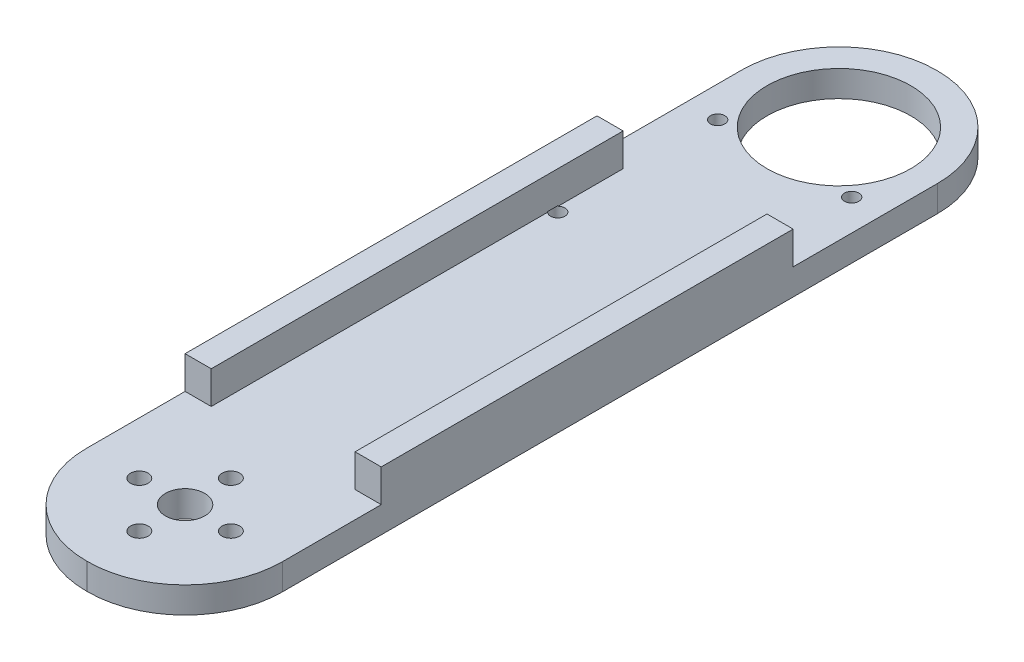
SolidWorks part; units mm, degrees
ref_plane "Front Plane" through (0, 0, 0) normal (0, 0, 1) x (1, 0, 0)
ref_plane "Top Plane" through (0, 0, 0) normal (0, 1, 0) x (1, 0, 0)
ref_plane "Right Plane" through (0, 0, 0) normal (1, 0, 0) x (0, 0, -1)
ref_plane "PY_p16_000" through (0, 16, 0) normal (0, 1, 0) x (1, 0, 0)
sketch "S_prism1" plane through (0, 16, 0) normal (0, 1, 0) x (1, 0, 0)
  line L0 (-0.1, -15) -> (0.1, -15)
  line L1 (15, -0.1) -> (15, 100.1)
  line L2 (0.1, 115) -> (-0.1, 115)
  line L3 (-15, 100.1) -> (-15, -0.1)
  arc A0 (-15, -0.1) -> (-0.1, -15) centre (-0.1, -0.1) ccw
  arc A1 (0.1, -15) -> (15, -0.1) centre (0.1, -0.1) ccw
  arc A2 (15, 100.1) -> (0.1, 115) centre (0.1, 100.1) ccw
  arc A3 (-0.1, 115) -> (-15, 100.1) centre (-0.1, 100.1) ccw
extrude "Boss_1" add sketch "S_prism1" along normal blind 4
ref_plane "PZ_m78_000" through (0, 0, -78) normal (0, 0, 1) x (1, 0, 0)
sketch "S_box2" plane through (0, 0, -78) normal (0, 0, 1) x (1, 0, 0)
  line L0 (-15, 19.5) -> (-11, 19.5)
  line L1 (-11, 19.5) -> (-11, 25)
  line L2 (-11, 25) -> (-15, 25)
  line L3 (-15, 25) -> (-15, 19.5)
  dimension "P1" = 15
  dimension "P2" = 19.5
  dimension "P3" = 11
  dimension "P4" = 19.5
  dimension "P5" = 11
  dimension "P6" = 25
  dimension "P7" = 15
  dimension "P8" = 25
extrude "Boss_2" add sketch "S_box2" along normal blind 63
sketch "S_box3" plane through (0, 0, -78) normal (0, 0, 1) x (1, 0, 0)
  line L0 (11, 19.5) -> (15, 19.5)
  line L1 (15, 19.5) -> (15, 25)
  line L2 (15, 25) -> (11, 25)
  line L3 (11, 25) -> (11, 19.5)
  dimension "P1" = 11
  dimension "P2" = 19.5
  dimension "P3" = 15
  dimension "P4" = 19.5
  dimension "P5" = 15
  dimension "P6" = 25
  dimension "P7" = 11
  dimension "P8" = 25
extrude "Boss_3" add sketch "S_box3" along normal blind 63
ref_plane "PY_p15_900" through (0, 15.9, 0) normal (0, 1, 0) x (1, 0, 0)
sketch "S_hole4" plane through (0, 15.9, 0) normal (0, 1, 0) x (1, 0, 0)
  circle A0 centre (0, 0) radius 3
  dimension "D1_S_hole4" = 6
extrude "Hole_4" cut sketch "S_hole4" along normal blind 4.2
sketch "S_hole5" plane through (0, 15.9, 0) normal (0, 1, 0) x (1, 0, 0)
  circle A0 centre (7, 0) radius 1.35
  dimension "D1_S_hole5" = 2.7
  dimension "P2" = 7
extrude "Hole_5" cut sketch "S_hole5" along normal blind 4.2
sketch "S_hole6" plane through (0, 15.9, 0) normal (0, 1, 0) x (1, 0, 0)
  circle A0 centre (0, -7) radius 1.35
  dimension "D1_S_hole6" = 2.7
  dimension "P2" = 7
extrude "Hole_6" cut sketch "S_hole6" along normal blind 4.2
sketch "S_hole7" plane through (0, 15.9, 0) normal (0, 1, 0) x (1, 0, 0)
  circle A0 centre (-7, 0) radius 1.35
  dimension "D1_S_hole7" = 2.7
  dimension "P2" = 7
extrude "Hole_7" cut sketch "S_hole7" along normal blind 4.2
sketch "S_hole8" plane through (0, 15.9, 0) normal (0, 1, 0) x (1, 0, 0)
  circle A0 centre (0, 7) radius 1.35
  dimension "D1_S_hole8" = 2.7
  dimension "P2" = 7
extrude "Hole_8" cut sketch "S_hole8" along normal blind 4.2
sketch "S_hole9" plane through (0, 15.9, 0) normal (0, 1, 0) x (1, 0, 0)
  circle A0 centre (0, 100) radius 11
  dimension "D1_S_hole9" = 22
  dimension "P2" = 100
extrude "Hole_9" cut sketch "S_hole9" along normal blind 4.2
sketch "S_hole10" plane through (0, 15.9, 0) normal (0, 1, 0) x (1, 0, 0)
  circle A0 centre (-10.25, 91.7) radius 1.1
  dimension "D1_S_hole10" = 2.2
  dimension "P2" = 10.25
  dimension "P3" = 91.7
extrude "Hole_10" cut sketch "S_hole10" along normal blind 4.2
sketch "S_hole11" plane through (0, 15.9, 0) normal (0, 1, 0) x (1, 0, 0)
  circle A0 centre (10.25, 91.7) radius 1.1
  dimension "D1_S_hole11" = 2.2
  dimension "P2" = 10.25
  dimension "P3" = 91.7
extrude "Hole_11" cut sketch "S_hole11" along normal blind 4.2
sketch "S_hole12" plane through (0, 15.9, 0) normal (0, 1, 0) x (1, 0, 0)
  circle A0 centre (-10.25, 67.25) radius 1.1
  dimension "D1_S_hole12" = 2.2
  dimension "P2" = 10.25
  dimension "P3" = 67.25
extrude "Hole_12" cut sketch "S_hole12" along normal blind 4.2
sketch "S_hole13" plane through (0, 15.9, 0) normal (0, 1, 0) x (1, 0, 0)
  circle A0 centre (10.25, 67.25) radius 1.1
  dimension "D1_S_hole13" = 2.2
  dimension "P2" = 10.25
  dimension "P3" = 67.25
extrude "Hole_13" cut sketch "S_hole13" along normal blind 4.2
equation "\"plate_t\" = 3"
equation "\"clearance\" = 0.4"
